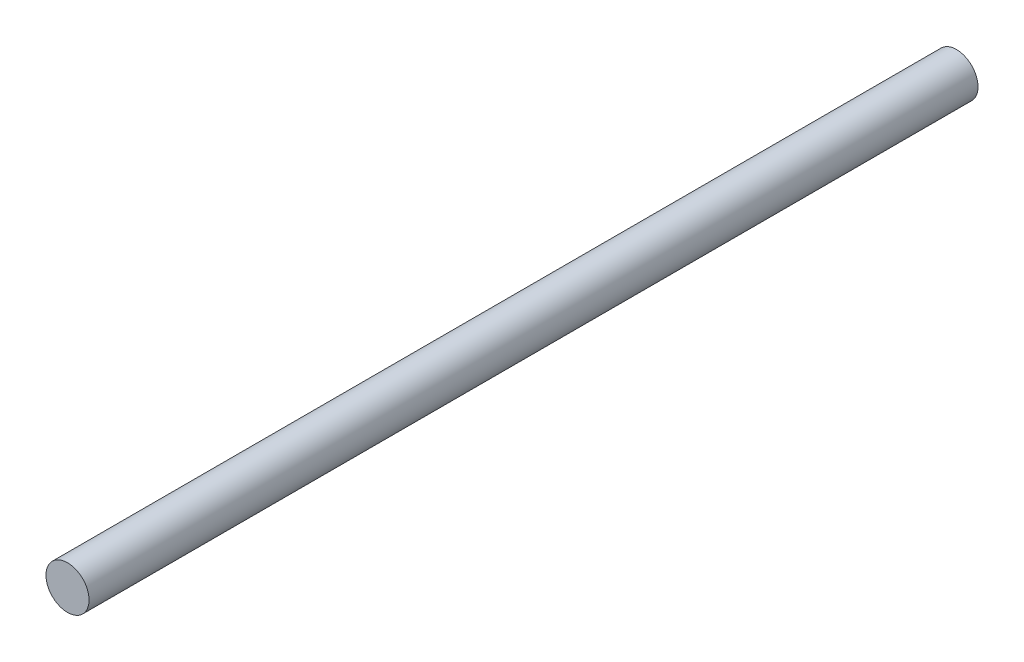
SolidWorks part; units mm, degrees
ref_plane "Спереди" through (0, 0, 0) normal (0, 0, 1) x (1, 0, 0)
ref_plane "Сверху" through (0, 0, 0) normal (0, 1, 0) x (1, 0, 0)
ref_plane "Справа" through (0, 0, 0) normal (1, 0, 0) x (0, 0, -1)
sketch "Эскиз1" plane through (0, 0, 0) normal (0, 0, 1) x (1, 0, 0)
  circle A0 centre (0, 0) radius 7
  circle A1 centre (0, 0) radius 8
  dimension "D1" = 14
  dimension "D2" = 1
extrude "Бобышка-Вытянуть3" add sketch "Эскиз1" along normal blind 165 and the other way blind 165 contours A1
